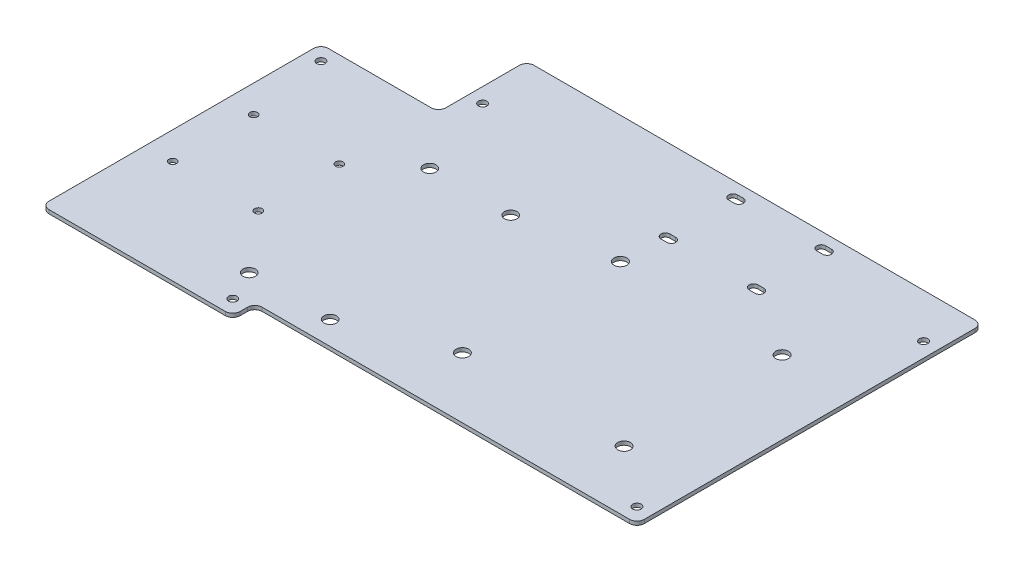
SolidWorks part; units mm, degrees
ref_plane "Front Plane" through (0, 0, 0) normal (0, 0, 1) x (1, 0, 0)
ref_plane "Top Plane" through (0, 0, 0) normal (0, 1, 0) x (1, 0, 0)
ref_plane "Right Plane" through (0, 0, 0) normal (1, 0, 0) x (0, 0, -1)
sketch "Sketch1" plane through (0, 0, 0) normal (0, 1, 0) x (1, 0, 0)
  line L1 (0, 0) -> (247.65, 0)
  line L2 (0, 0) -> (0, 120.65)
  line L3 (50.8, 158.75) -> (247.65, 158.75)
  line L4 (247.65, 0) -> (247.65, 158.75)
  line L15 (0, 120.65) -> (50.8, 120.65)
  line L16 (50.8, 158.75) -> (50.8, 120.65)
  line L21 (351.9786, 184.7613) -> (351.9786, -3.4747) construction
  dimension "D1" = 158.75
  dimension "D2" = 351.9786
  dimension "D4" = 247.65
  dimension "D6" = 38.1
  dimension "D7" = 50.8
extrude "Boss-Extrude1" add sketch "Sketch1" along normal blind 1.6002 contours L1 L4 L3 L2 L15 L16 region at (128.9214, 0, -76.2514)
sketch "Sketch3" plane through (0, 1.6002, 0) normal (0, 1, 0) x (1, 0, 0)
  line L0 (82.55, 0) -> (82.55, 9.525)
  line L1 (0, 0) -> (247.65, 0) construction
  line L2 (82.55, 9.525) -> (247.65, 9.525)
  line L8 (247.65, 0) -> (247.65, 158.75) construction
  line L10 (247.65, 0) -> (82.55, 0)
  line L11 (0, 0) -> (0, 120.65) construction
  line L12 (247.65, 9.525) -> (247.65, 0)
  dimension "D1" = 82.55
  dimension "D2" = 9.525
extrude "Cut-Extrude1" cut sketch "Sketch3" against normal through all
fillet "Fillet1" radius 3.175 8 edges at (82.55, 0.8001, 0) (0, 0.8001, -120.65) (50.8, 0.8001, -120.65) (50.8, 0.8001, -158.75) (247.65, 0.8001, -158.75) (247.65, 0.8001, -9.525) (82.55, 0.8001, -9.525) (0, 0.8001, 0)
sketch "Sketch4" plane through (0, 1.6002, 0) normal (0, 1, 0) x (1, 0, 0)
  line L0 (146.365, 152.32) -> (148.905, 152.32) construction
  line L1 (146.365, 154.225) -> (148.905, 154.225)
  line L2 (146.365, 150.415) -> (148.905, 150.415)
  line L5 (184.465, 152.32) -> (187.005, 152.32) construction
  line L6 (184.465, 154.225) -> (187.005, 154.225)
  line L7 (184.465, 150.415) -> (187.005, 150.415)
  line L8 (184.465, 123.11) -> (187.005, 123.11) construction
  line L9 (184.465, 125.015) -> (187.005, 125.015)
  line L10 (184.465, 121.205) -> (187.005, 121.205)
  line L11 (146.365, 123.11) -> (148.905, 123.11) construction
  line L12 (146.365, 125.015) -> (148.905, 125.015)
  line L13 (146.365, 121.205) -> (148.905, 121.205)
  line L15 (185.735, 123.11) -> (147.635, 123.11) construction
  line L16 (185.735, 123.11) -> (185.735, 152.32) construction
  line L17 (185.735, 152.32) -> (147.635, 152.32) construction
  line L18 (147.635, 123.11) -> (147.635, 152.32) construction
  line L19 (185.735, 123.11) -> (147.635, 152.32) construction
  line L20 (185.735, 152.32) -> (147.635, 123.11) construction
  line L21 (203.2, 125.015) -> (130.17, 125.015) construction
  line L22 (203.2, 125.015) -> (203.2, 150.415) construction
  line L23 (203.2, 150.415) -> (130.17, 150.415) construction
  line L24 (130.17, 125.015) -> (130.17, 150.415) construction
  line L25 (203.2, 125.015) -> (130.17, 150.415) construction
  line L26 (203.2, 150.415) -> (130.17, 125.015) construction
  arc A0 (146.365, 154.225) -> (146.365, 150.415) centre (146.365, 152.32) ccw
  arc A1 (148.905, 150.415) -> (148.905, 154.225) centre (148.905, 152.32) ccw
  arc A2 (184.465, 154.225) -> (184.465, 150.415) centre (184.465, 152.32) ccw
  arc A3 (187.005, 150.415) -> (187.005, 154.225) centre (187.005, 152.32) ccw
  arc A4 (184.465, 125.015) -> (184.465, 121.205) centre (184.465, 123.11) ccw
  arc A5 (187.005, 121.205) -> (187.005, 125.015) centre (187.005, 123.11) ccw
  arc A6 (146.365, 125.015) -> (146.365, 121.205) centre (146.365, 123.11) ccw
  arc A7 (148.905, 121.205) -> (148.905, 125.015) centre (148.905, 123.11) ccw
  point P2 (147.635, 152.32)
  point P12 (166.685, 137.715)
  point P13 (185.735, 152.32)
  point P20 (185.735, 123.11)
  point P27 (147.635, 123.11)
  point P36 (166.685, 137.715)
  dimension "D2" = 6.35
  dimension "D1" = 3.81
  dimension "D5" = 38.1
  dimension "D3" = 2
  dimension "D4" = 2
extrude "Fuse Ziptie Mounts" cut sketch "Sketch4" against normal through all
sketch "Sketch5" plane through (0, 1.6002, 0) normal (0, 1, 0) x (1, 0, 0)
  circle A0 centre (146.05, 103.9876) radius 2.75
  circle A1 centre (146.05, 35.7124) radius 2.75
  circle A2 centre (215.9, 103.9876) radius 2.75
  circle A3 centre (215.9, 35.7124) radius 2.75
  dimension "D1" = 5.5
extrude "Contactor Mounting Holes" cut sketch "Sketch5" against normal through all
sketch "Sketch6" plane through (0, 1.6002, 0) normal (0, 1, 0) x (1, 0, 0)
  line L0 (0, 3.175) -> (0, 117.475) construction
  line L1 (3.175, 120.65) -> (47.625, 120.65) construction
  line L2 (82.55, 6.35) -> (82.55, 3.175) construction
  line L3 (3.175, 0) -> (79.375, 0) construction
  line L4 (244.475, 9.525) -> (85.725, 9.525) construction
  line L5 (247.65, 12.7) -> (247.65, 155.575) construction
  line L6 (53.975, 158.75) -> (244.475, 158.75) construction
  line L7 (50.8, 155.575) -> (50.8, 123.825) construction
  circle A0 centre (6.35, 114.3) radius 1.8288
  circle A1 centre (76.2, 6.35) radius 1.8288
  circle A2 centre (241.3, 15.875) radius 1.8288
  circle A3 centre (241.3, 139.7) radius 1.8288
  circle A4 centre (57.15, 133.35) radius 1.8288
  dimension "D1" = 3.6576
  dimension "D2" = 6.35
  dimension "D3" = 6.35
  dimension "D4" = 6.35
  dimension "D5" = 6.35
  dimension "D6" = 6.35
  dimension "D7" = 6.35
  dimension "D8" = 19.05
  dimension "D9" = 6.35
  dimension "D10" = 25.4
extrude "Cut-Extrude2" cut sketch "Sketch6" against normal through all
sketch "Sketch7" plane through (0, 1.6002, 0) normal (0, 1, 0) x (1, 0, 0)
  line L0 (70, 97.65) -> (70, 19.65) construction
  line L1 (105, 19.65) -> (105, 97.65) construction
  circle A0 centre (105, 19.65) radius 2.7051
  circle A1 centre (70, 19.65) radius 2.7051
  circle A2 centre (105, 97.65) radius 2.7051
  circle A3 centre (70, 97.65) radius 2.7051
  point P2 (0, 0)
  dimension "D1" = 5.4102
  dimension "D2" = 35
extrude "Cut-Extrude3" cut sketch "Sketch7" against normal through all
sketch "Sketch9" plane through (0, 1.6002, 0) normal (0, 1, 0) x (1, 0, 0)
  circle A0 centre (11.85, 79.75) radius 1.65
  circle A1 centre (11.85, 44.75) radius 1.65
  circle A2 centre (48.85, 79.75) radius 1.65
  circle A3 centre (48.85, 44.75) radius 1.65
  dimension "D1" = 3.3
extrude "Cut-Extrude4" cut sketch "Sketch9" against normal through all
